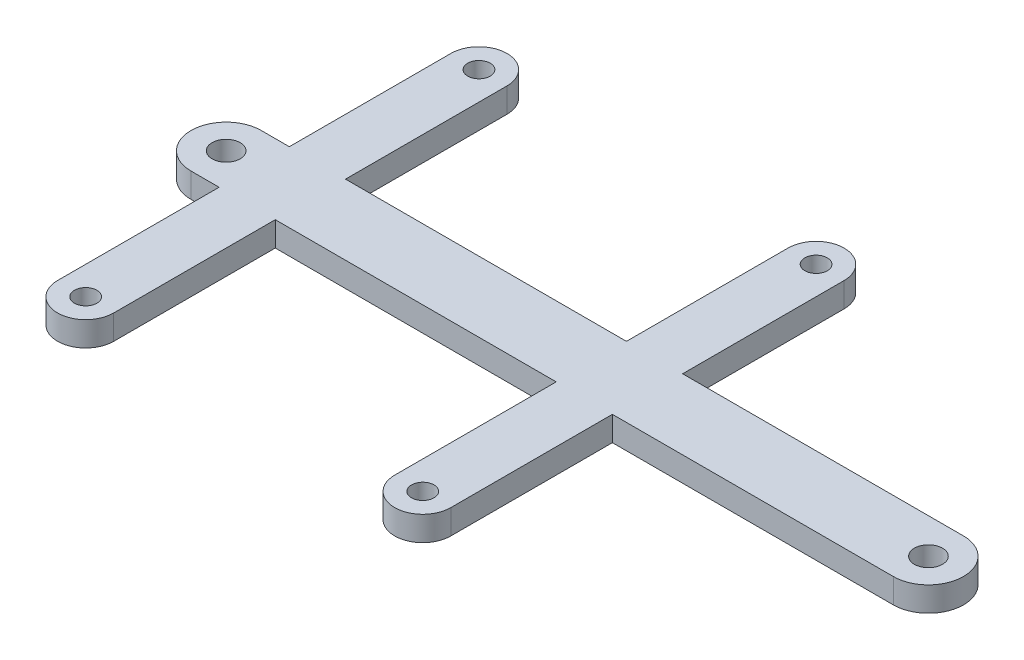
SolidWorks part; units mm, degrees
ref_plane "Front Plane" through (0, 0, 0) normal (0, 0, 1) x (1, 0, 0)
ref_plane "Top Plane" through (0, 0, 0) normal (0, 1, 0) x (1, 0, 0)
ref_plane "Right Plane" through (0, 0, 0) normal (1, 0, 0) x (0, 0, -1)
sketch "Sketch1" plane through (0, 0, 0) normal (0, 1, 0) x (1, 0, 0)
  line L0 (10, 28) -> (10, 5)
  line L4 (2, 28) -> (2, 5)
  line L5 (50, 5) -> (10, 5)
  line L16 (-50, 5) -> (-46, 5)
  line L17 (-38, 28) -> (-38, 5)
  line L18 (-46, 28) -> (-46, 5)
  line L19 (-38, 5) -> (2, 5)
  line L20 (0, 0) -> (15.6134, 0)
  line L21 (-38, -5) -> (2, -5)
  line L22 (-46, -28) -> (-46, -5)
  line L23 (-38, -28) -> (-38, -5)
  line L24 (50, -5) -> (10, -5)
  line L25 (2, -28) -> (2, -5)
  line L26 (10, -28) -> (10, -5)
  line L27 (-46, -5) -> (-50, -5)
  circle A0 centre (50, 0) radius 2
  arc A1 (50, -5) -> (50, 5) centre (50, 0) ccw
  arc A6 (-50, -5) -> (-50, 5) centre (-50, 0) cw
  circle A7 centre (-50, 0) radius 2
  circle A12 centre (6, 28) radius 1.6
  arc A13 (10, 28) -> (2, 28) centre (6, 28) ccw
  arc A14 (-38, 28) -> (-46, 28) centre (-42, 28) ccw
  circle A15 centre (-42, 28) radius 1.6
  circle A16 centre (-42, -28) radius 1.6
  arc A17 (-38, -28) -> (-46, -28) centre (-42, -28) cw
  arc A18 (10, -28) -> (2, -28) centre (6, -28) cw
  circle A19 centre (6, -28) radius 1.6
extrude "Boss-Extrude1" add sketch "Sketch1" along normal blind 3.5 contours A18 L26 L24 A1 L5 L0 A13 L4 L19 L17 A14 L18 L16 A6 L27 L22 A17 L23 L21 L25 A16 A15 A12 A0 A7 A19 region at (-7.7935, 0, 0)
